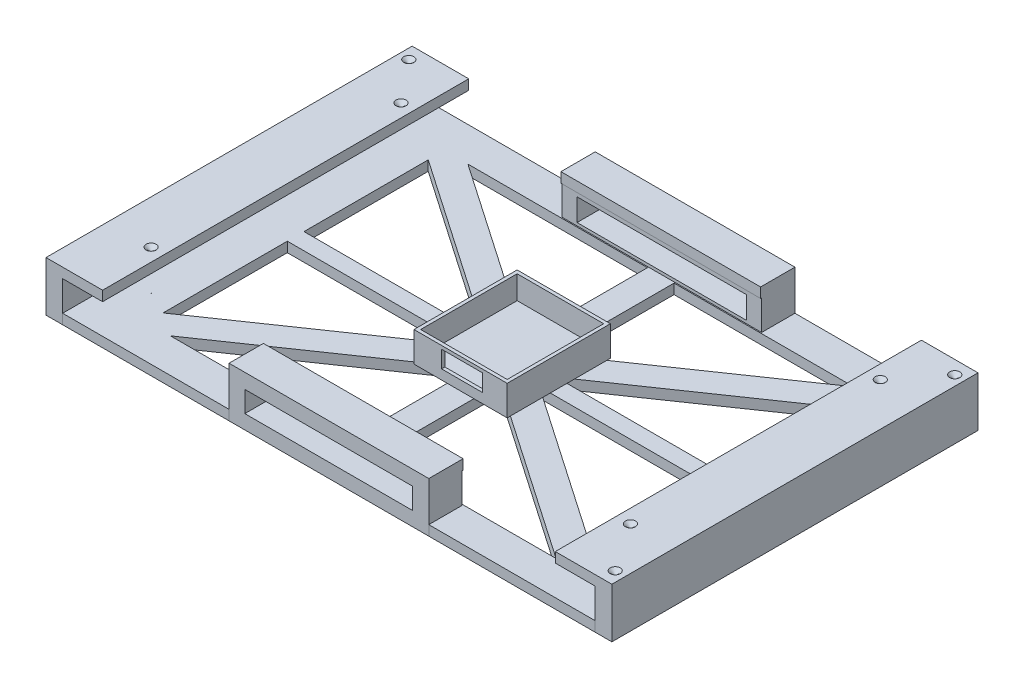
SolidWorks part; units mm, degrees
ref_plane "Front Plane" through (0, 0, 0) normal (0, 0, 1) x (1, 0, 0)
ref_plane "Top Plane" through (0, 0, 0) normal (0, 1, 0) x (1, 0, 0)
ref_plane "Right Plane" through (0, 0, 0) normal (1, 0, 0) x (0, 0, -1)
sketch "Sketch1" plane through (0, 0, 0) normal (0, 1, 0) x (1, 0, 0)
  line L0 (80, 110) -> (80, 0) construction
  line L1 (0, 0) -> (160, 0)
  line L2 (0, 0) -> (0, 110)
  line L3 (0, 110) -> (160, 110)
  line L4 (160, 0) -> (160, 110)
  line L9 (80, 110) -> (80, 0)
  line L10 (0, 55) -> (160, 55)
  line L11 (0, 110) -> (160, 0)
  line L12 (0, 0) -> (160, 110)
  line L13 (0, 52.5) -> (160, 52.5)
  line L14 (0, 57.5) -> (160, 57.5)
  line L15 (0, 105.1459) -> (152.9395, 0)
  line L16 (7.0605, 110) -> (160, 4.8541)
  line L17 (76, 110) -> (76, 0)
  line L18 (7.0605, 0) -> (160, 105.1459)
  line L19 (84, 110) -> (84, 0)
  line L20 (0, 4.8541) -> (152.9395, 110)
  line L21 (2.2661, 113.2962) -> (162.2661, 3.2962) construction
  line L22 (-2.2661, 106.7038) -> (157.7339, -3.2962) construction
  line L23 (-2.2661, 3.2962) -> (157.7339, 113.2962) construction
  line L24 (2.2661, -3.2962) -> (162.2661, 106.7038) construction
  line L26 (15, 10.3125) -> (145, 10.3125)
  line L27 (15, 10.3125) -> (15, 99.6875)
  line L28 (15, 99.6875) -> (145, 99.6875)
  line L29 (145, 10.3125) -> (145, 99.6875)
  line L30 (15, 10.3125) -> (145, 99.6875) construction
  line L31 (15, 99.6875) -> (145, 10.3125) construction
  line L32 (0, 110) -> (-5, 110)
  line L33 (0, 110) -> (0, 0)
  line L34 (0, 0) -> (-5, 0)
  line L35 (-5, 110) -> (-5, 0)
  line L36 (160, 0) -> (165, 0)
  line L37 (160, 0) -> (160, 110)
  line L38 (160, 110) -> (160, 0)
  line L39 (50, 0) -> (110, 0)
  line L40 (50, 100) -> (110, 100)
  line L41 (50, 100) -> (50, 110)
  line L42 (50, 110) -> (110, 110)
  line L43 (110, 100) -> (110, 110)
  line L44 (50, 100) -> (110, 110) construction
  line L45 (50, 110) -> (110, 100) construction
  line L46 (110, 10) -> (110, 0)
  line L47 (50, 10) -> (110, 10)
  line L48 (50, 10) -> (50, 0)
  line L49 (160, 110) -> (165, 110)
  line L50 (165, 0) -> (165, 110)
  point P33 (80, 55)
  point P42 (80, 105)
  dimension "D1" = 160
  dimension "D2" = 110
  dimension "D9" = 15
  dimension "D10" = 5
  dimension "D11" = 60
  dimension "D12" = 10
  dimension "D13" = 5
  dimension "D3" = 2.5
  dimension "D4" = 2.5
  dimension "D5" = 4
  dimension "D6" = 4
  dimension "D7" = 4
  dimension "D8" = 4
extrude "Boss-Extrude1" add sketch "Sketch1" along normal blind 3 contours L14 L27 L15 L2 | L20 L27 L13 L2 | L48 L47 L17 L26 L18 L1 | L19 L47 L46 L1 L15 L26 | L29 L16 L4 L13 | L29 L14 L4 L18 | L43 L40 L19 L28 L20 L3 | L40 L41 L3 L16 L28 L17 | L11 L28 L16 L3 | L15 L27 L11 L2 | L26 L12 L1 L18 | L12 L27 L20 L2 | L29 L11 L4 L16 | L26 L15 L1 L11 | L29 L10 L4 L14 | L29 L13 L4 L10 | L20 L28 L12 L3 | L29 L18 L4 L12 | L10 L27 L14 L2 | L13 L27 L10 L2 | L27 L12 L17 L13 L20 | L12 L26 L18 L17 | L17 L26 L9 L18 | L9 L26 L19 L15 | L15 L26 L11 L19 | L11 L29 L16 L13 L19 | L17 L47 L9 L26 | L9 L47 L19 L26 | L13 L29 L10 L16 | L10 L29 L14 L18 | L18 L29 L12 L19 L14 | L28 L20 L19 L12 | L28 L9 L20 L19 | L28 L17 L16 L9 | L28 L11 L17 L16 | L27 L15 L14 L17 L11 | L40 L9 L28 L19 | L40 L17 L28 L9 | L27 L10 L15 L14 | L27 L13 L20 L10 | L14 L20 L16 L17 L11 | L15 L20 L17 L14 | L20 L13 L17 L15 | L17 L10 L15 | L20 L10 L17 | L17 L18 L15 L13 L12 | L13 L15 L9 | L9 L18 L13 | L19 L11 L13 L18 L15 | L19 L10 L11 L18 | L13 L18 L11 L9 | L12 L15 L13 L9 | L10 L17 L15 L12 | L20 L17 L10 L11 | L20 L11 L9 L14 | L20 L14 L9 | L16 L14 L9 L12 | L16 L9 L14 | L20 L16 L14 L12 L19 | L14 L19 L16 L18 | L16 L19 L10 | L10 L19 L18 | L18 L19 L13 L16 | L19 L16 L12 L10 | L11 L17 L14 | L17 L20 L11 L14 | L11 L20 L14 | L15 L17 L13 L12 | L13 L17 L12 | L15 L12 L13 | L18 L13 L11 | L19 L18 L11 L13 | L19 L13 L11 | L19 L12 L14 | L19 L14 L12 L16 | L14 L16 L12 region at (11.0303, 0, -5.1563) region at (7.5, 0, -7.5833) region at (32.6896, 0, -4.9092) region at (7.1966, 0, -31.1509) region at (43.9474, 0, -32.5919) region at (47.229, 0, -30.0926) region at (7.5, 0, -53.75) region at (76.1212, 0, -52.4167) region at (77.3504, 0, -50.1102) region at (78.0238, 0, -29.5499) region at (78, 0, -10.1562) region at (7.5, 0, -56.25) region at (43.0705, 0, -53.7635) region at (72.8982, 0, -53.3422) region at (76.1717, 0, -52.6398) region at (76.4697, 0, -52.5243) region at (7.5, 0, -102.4167) region at (11.0303, 0, -104.8437) region at (78.8586, 0, -51.7153) region at (81.9762, 0, -29.5499) region at (82.6496, 0, -50.1102) region at (81.1414, 0, -51.7153) region at (82, 0, -10.1562) region at (7.1966, 0, -78.8491) region at (43.0705, 0, -56.2365) region at (74.9798, 0, -55.7014) region at (74.9798, 0, -54.2986) region at (72.8982, 0, -56.6578) region at (77.3667, 0, -54.1262) region at (78.7918, 0, -53.3347) region at (32.6896, 0, -105.0908) region at (47.229, 0, -79.9074) region at (43.9474, 0, -77.4081) region at (81.2082, 0, -53.3347) region at (112.771, 0, -30.0926) region at (83.5303, 0, -52.5243) region at (127.3104, 0, -4.9092) region at (77.3667, 0, -55.8738) region at (76.1717, 0, -57.3602) region at (78.7918, 0, -56.6653) region at (82.6333, 0, -55.8738) region at (82.6333, 0, -54.1262) region at (81.2082, 0, -56.6653) region at (77.3504, 0, -59.8898) region at (76.1212, 0, -57.5833) region at (148.9697, 0, -5.1562) region at (116.0526, 0, -32.5919) region at (83.8788, 0, -52.4167) region at (83.8283, 0, -52.6398) region at (76.4697, 0, -57.4757) region at (78.8586, 0, -58.2847) region at (81.1414, 0, -58.2847) region at (85.0202, 0, -55.7014) region at (85.0202, 0, -54.2986) region at (83.5303, 0, -57.4757) region at (83.8283, 0, -57.3602) region at (78.0238, 0, -80.4501) region at (78, 0, -99.8437) region at (152.5, 0, -7.5833) region at (87.1018, 0, -53.3422)
extrude "Boss-Extrude2" add sketch "Sketch1<5>" along normal blind 12 separate body contours L32 L35 L34 L2 | L36 L50 L49 L4 | L40 L43 L42 L41 | L47 L46 L39 L48 region at (-2.5, 0, -55) region at (162.5, 0, -55)
sketch "Sketch1<5>" plane through (0, 0, 0) normal (0, 1, 0) x (1, 0, 0) same geometry as "Sketch1"
sketch "Sketch2" plane through (0, 12, 0) normal (0, 1, 0) x (1, 0, 0)
  line L0 (0, 0) -> (50, 0) construction
  line L1 (-5, 110) -> (12, 110)
  line L2 (-5, 110) -> (-5, 0)
  line L3 (-5, 0) -> (12, 0)
  line L4 (12, 110) -> (12, 0)
  line L5 (110, 0) -> (160, 0) construction
  line L6 (165, 110) -> (148, 110)
  line L7 (165, 110) -> (165, 0)
  line L8 (165, 0) -> (148, 0)
  line L9 (148, 110) -> (148, 0)
  line L10 (84, 99.6875) -> (137.9395, 99.6875) construction
  line L11 (50, 110) -> (110, 110)
  line L12 (50, 110) -> (50, 99.6875)
  line L13 (50, 99.6875) -> (110, 99.6875)
  line L14 (110, 110) -> (110, 99.6875)
  line L15 (84, 10.3125) -> (137.9395, 10.3125) construction
  line L16 (50, 0) -> (110, 0)
  line L17 (50, 0) -> (50, 10.3125)
  line L18 (50, 10.3125) -> (110, 10.3125)
  line L19 (110, 0) -> (110, 10.3125)
  dimension "D1" = 17
  dimension "D2" = 17
extrude "Boss-Extrude3" add sketch "Sketch2" along normal blind 3
sketch "Sketch3" plane through (0, 0, 0) normal (0, 0, 1) x (1, 0, 0)
  line L1 (54.7315, 10.5657) -> (105.0827, 10.5657)
  line L2 (54.7315, 10.5657) -> (54.7315, 4.2485)
  line L3 (54.7315, 4.2485) -> (105.0827, 4.2485)
  line L4 (105.0827, 10.5657) -> (105.0827, 4.2485)
extrude "Cut-Extrude1" cut sketch "Sketch3" against normal blind 12
sketch "Sketch4" plane through (0, 0, -110) normal (0, 0, -1) x (-1, 0, 0)
  line L1 (-105.4543, 10.5657) -> (-54.5457, 10.5657)
  line L2 (-105.4543, 10.5657) -> (-105.4543, 3.8769)
  line L3 (-105.4543, 3.8769) -> (-54.5457, 3.8769)
  line L4 (-54.5457, 10.5657) -> (-54.5457, 3.8769)
extrude "Cut-Extrude2" cut sketch "Sketch4" against normal blind 12
sketch "Sketch5" plane through (0, 3, 0) normal (0, 1, 0) x (1, 0, 0)
  line L0 (80, 99.6875) -> (80, 10.4083) construction
  line L1 (50, 99.6875) -> (110, 99.6875) construction
  line L2 (12, 0) -> (12, 110) construction
  line L3 (12, 55) -> (148, 55) construction
  line L4 (148, 110) -> (148, 0) construction
  line L6 (66, 39.5479) -> (94, 39.5479)
  line L7 (66, 39.5479) -> (66, 70.5479)
  line L8 (66, 70.5479) -> (94, 70.5479)
  line L9 (94, 39.5479) -> (94, 70.5479)
  line L10 (66, 39.5479) -> (94, 70.5479) construction
  line L11 (66, 70.5479) -> (94, 39.5479) construction
  point P10 (80, 55.0479)
  dimension "D1" = 28
  dimension "D2" = 31
extrude "Boss-Extrude4" add sketch "Sketch5" along normal blind 9
sketch "Sketch6" plane through (0, 12, 0) normal (0, 1, 0) x (1, 0, 0)
  line L1 (67, 69.5479) -> (93, 69.5479)
  line L2 (67, 69.5479) -> (67, 40.5479)
  line L3 (67, 40.5479) -> (93, 40.5479)
  line L4 (93, 69.5479) -> (93, 40.5479)
  line L7 (94, 70.5479) -> (66, 70.5479) construction
  line L8 (66, 70.5479) -> (66, 39.5479) construction
  dimension "D1" = 26
  dimension "D2" = 29
  dimension "D3" = 1
  dimension "D4" = 1
extrude "Cut-Extrude3" cut sketch "Sketch6" against normal blind 7
sketch "Sketch7" plane through (0, 0, -39.5479) normal (0, 0, 1) x (1, 0, 0)
  line L1 (74.2915, 11.016) -> (86.613, 11.016)
  line L2 (74.2915, 11.016) -> (74.2915, 5.8961)
  line L3 (74.2915, 5.8961) -> (86.613, 5.8961)
  line L4 (86.613, 11.016) -> (86.613, 5.8961)
extrude "Cut-Extrude4" cut sketch "Sketch7" against normal blind 2
hole_wizard "#97 (0.0059) Diameter Hole2" positions "Sketch13" profile "Sketch14" hole size "#97" standard "ANSI Inch" end condition through all
sketch "Sketch13" plane through (0, 15, 0) normal (0, 1, 0) x (1, 0, 0)
  point P0 (-2, 106)
sketch "Sketch14" plane through (-2, 15, -106) normal (1, 0, 0) x (0, 0, 1)
  line L0 (0, 0) -> (0, 15)
  line L1 (0, 15) -> (0.0749, 15)
  line L2 (0.0749, 15) -> (0.0749, 1.2053)
  line L3 (0.0749, 1.2053) -> (1.5113, 0)
  line L5 (1.5113, 0) -> (0, 0)
  line L6 (-0.0749, 1.2053) -> (-1.5113, 0) construction
  line L11 (0, -6.35) -> (0, 107.95) construction
  dimension "Thru Hole Dia." = 0.1499
  dimension "Thru Hole Depth" = 15
  dimension "Near C'Sink Dia." = 3.0226
  dimension "Near C'Sink Angle" = 100
hole_wizard "#97 (0.0059) Diameter Hole4" positions "Sketch17" profile "Sketch18" hole size "#97" standard "ANSI Inch" end condition through all
sketch "Sketch17" plane through (0, 15, 0) normal (0, 1, 0) x (1, 0, 0)
  point P0 (162, 106)
sketch "Sketch18" plane through (162, 15, -106) normal (1, 0, 0) x (0, 0, 1)
  line L0 (0, 0) -> (0, 15)
  line L1 (0, 15) -> (0.0749, 15)
  line L2 (0.0749, 15) -> (0.0749, 1.2053)
  line L3 (0.0749, 1.2053) -> (1.5113, 0)
  line L5 (1.5113, 0) -> (0, 0)
  line L6 (-0.0749, 1.2053) -> (-1.5113, 0) construction
  line L11 (0, -6.35) -> (0, 107.95) construction
  dimension "Thru Hole Dia." = 0.1499
  dimension "Thru Hole Depth" = 15
  dimension "Near C'Sink Dia." = 3.0226
  dimension "Near C'Sink Angle" = 100
hole_wizard "#97 (0.0059) Diameter Hole5" positions "Sketch19" profile "Sketch20" hole size "#97" standard "ANSI Inch" end condition through all
sketch "Sketch19" plane through (0, 15, 0) normal (0, 1, 0) x (1, 0, 0)
  point P0 (162, 4)
sketch "Sketch20" plane through (162, 15, -4) normal (1, 0, 0) x (0, 0, 1)
  line L0 (0, 0) -> (0, 15)
  line L1 (0, 15) -> (0.0749, 15)
  line L2 (0.0749, 15) -> (0.0749, 1.2053)
  line L3 (0.0749, 1.2053) -> (1.5113, 0)
  line L5 (1.5113, 0) -> (0, 0)
  line L6 (-0.0749, 1.2053) -> (-1.5113, 0) construction
  line L11 (0, -6.35) -> (0, 107.95) construction
  dimension "Thru Hole Dia." = 0.1499
  dimension "Thru Hole Depth" = 15
  dimension "Near C'Sink Dia." = 3.0226
  dimension "Near C'Sink Angle" = 100
hole_wizard "#97 (0.0059) Diameter Hole9" positions "Sketch30" profile "Sketch31" hole size "#97" standard "ANSI Inch" end condition through all
sketch "Sketch30" plane through (0, 15, 0) normal (0, 1, 0) x (1, 0, 0)
  point P0 (8.0963, 93.553)
  point P2 (8.0963, 18.4907)
  point P4 (152.0895, 18.4907)
  point P6 (152.0895, 93.553)
sketch "Sketch31" plane through (8.0963, 15, -93.553) normal (1, 0, 0) x (0, 0, 1)
  line L0 (0, 0) -> (0, 15)
  line L1 (0, 15) -> (0.0749, 15)
  line L2 (0.0749, 15) -> (0.0749, 1.2053)
  line L3 (0.0749, 1.2053) -> (1.5113, 0)
  line L5 (1.5113, 0) -> (0, 0)
  line L6 (-0.0749, 1.2053) -> (-1.5113, 0) construction
  line L11 (0, -6.35) -> (0, 107.95) construction
  dimension "Thru Hole Dia." = 0.1499
  dimension "Thru Hole Depth" = 15
  dimension "Near C'Sink Dia." = 3.0226
  dimension "Near C'Sink Angle" = 100
